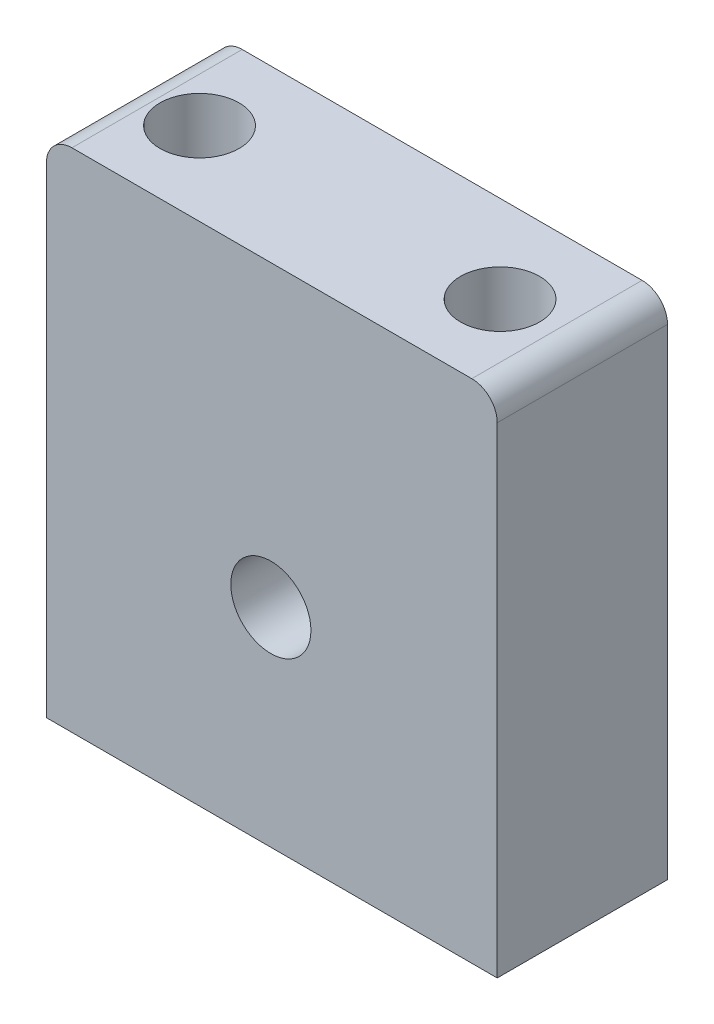
SolidWorks part; units mm, degrees
ref_plane "Front Plane" through (0, 0, 0) normal (0, 0, 1) x (1, 0, 0)
ref_plane "Top Plane" through (0, 0, 0) normal (0, 1, 0) x (1, 0, 0)
ref_plane "Right Plane" through (0, 0, 0) normal (1, 0, 0) x (0, 0, -1)
sketch "Sketch1" plane through (0, 0, 0) normal (0, 0, 1) x (1, 0, 0)
  line L1 (0, 0) -> (45, 0)
  line L2 (0, 0) -> (0, 50.8)
  line L3 (0, 50.8) -> (45, 50.8)
  line L4 (45, 0) -> (45, 50.8)
  circle A0 centre (22.4, 21) radius 4
  dimension "D3" = 8
  dimension "D1" = 45
  dimension "D2" = 50.8
  dimension "D4" = 21
  dimension "D5" = 22.4
extrude "Boss-Extrude1" add sketch "Sketch1" along normal blind 17
sketch "Sketch2" plane through (0, 50.8, 0) normal (0, 1, 0) x (1, 0, 0)
  line L0 (0, -17) -> (0, 0) construction
  circle A0 centre (7, -8.7186) radius 3.95
  circle A1 centre (37, -8.7186) radius 3.95
  dimension "D1" = 7.9
  dimension "D3" = 7.9
  dimension "D2" = 7
  dimension "D4" = 30
extrude "Cut-Extrude1" cut sketch "Sketch2" against normal blind 17
fillet "Fillet1" radius 2.54 2 edges at (0, 50.8, 8.5) (45, 50.8, 8.5)
sketch "Sketch3" plane through (45, 0, 0) normal (1, 0, 0) x (0, 0, -1)
  line L0 (-17, 0) -> (-17, 48.26) construction
  line L1 (0, 0) -> (-17, 0)
  line L2 (0, 0) -> (0, 0.254)
  line L3 (0, 0.254) -> (-17, 0.254)
  line L4 (-17, 0) -> (-17, 0.254)
  dimension "D1" = 0.254
extrude "Cut-Extrude2" cut sketch "Sketch3" against normal through all
